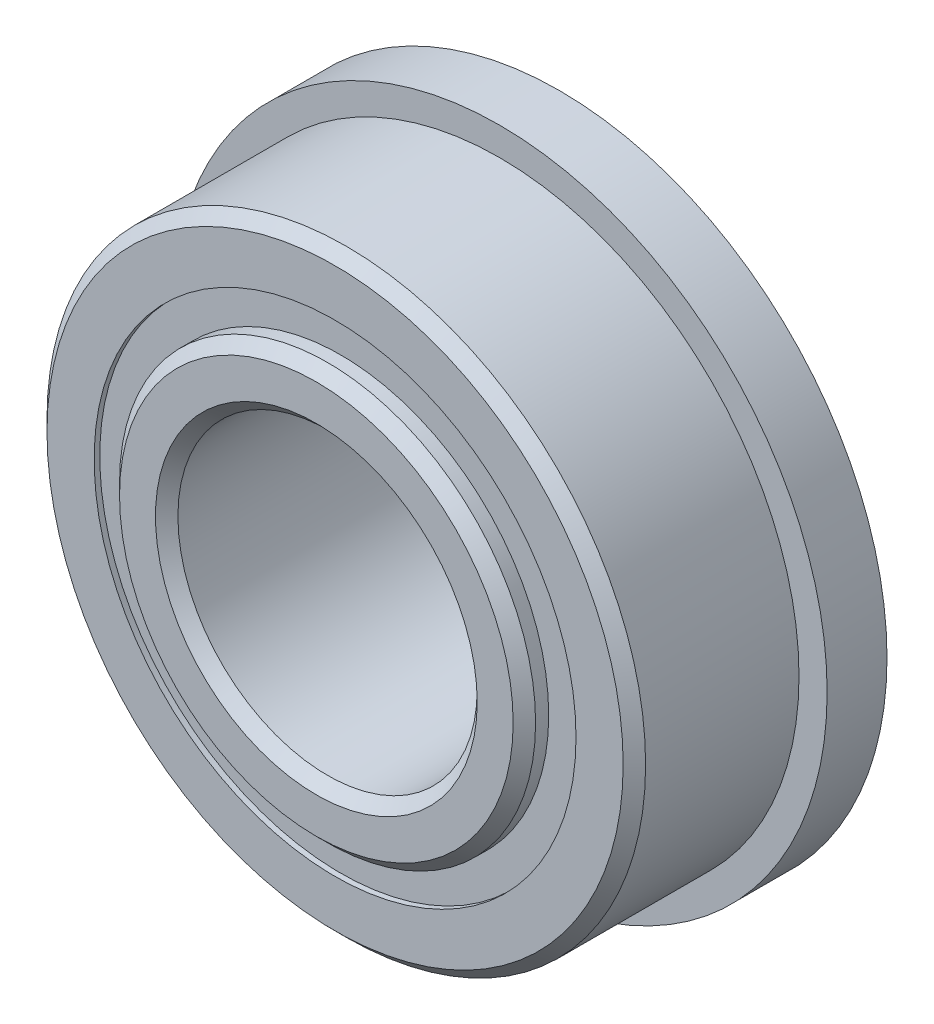
SolidWorks part; units mm, degrees
ref_plane "Front Plane" through (0, 0, 0) normal (0, 0, 1) x (1, 0, 0)
ref_plane "Top Plane" through (0, 0, 0) normal (0, 1, 0) x (1, 0, 0)
ref_plane "Right Plane" through (0, 0, 0) normal (1, 0, 0) x (0, 0, -1)
sketch "Sketch1" plane through (0, 0, 0) normal (1, 0, 0) x (0, 0, -1)
  line L0 (-2.3813, 0) -> (2.3813, 0) construction
  line L1 (0, 6.35) -> (0, -6.35) construction
  line L2 (2.1431, 6.35) -> (-2.1431, 6.35)
  line L3 (-2.1431, 6.35) -> (-2.3813, 6.1119)
  line L4 (-2.3813, 6.1119) -> (-2.3813, 5.1114)
  line L5 (-2.3813, 5.1114) -> (-1.0583, 5.1114)
  line L6 (2.3813, 5.1114) -> (1.0583, 5.1114)
  line L7 (2.3813, 6.1119) -> (2.3813, 5.1114)
  line L8 (2.1431, 6.35) -> (2.3813, 6.1119)
  line L9 (0, 6.35) -> (0, 4.7625) construction
  line L10 (0, 4.7625) -> (0, 3.175) construction
  arc A0 (-1.0583, 5.1114) -> (1.0583, 5.1114) centre (0, 4.7625) cw
  point P14 (0, 3.175)
  dimension "D3" = 2.1167
  dimension "D1" = 45
  dimension "Width" = 4.7625
  dimension "OD" = 12.7
  dimension "D2" = 0.2381
  dimension "Shaft Dia" = 6.35
  dimension "D4" = 0.3489
revolve "Revolve1" add sketch "Sketch1" angle 360 about L0
sketch "Sketch3" plane through (0, 0, 0) normal (1, 0, 0) x (0, 0, -1)
  line L0 (-1.0583, 4.4136) -> (-2.7788, 4.4136) construction
  line L1 (-2.3813, 6.1119) -> (-2.3813, 5.1114) construction
  line L2 (-2.1431, 6.35) -> (-2.3813, 6.1119) construction
  line L3 (-2.7788, 4.4136) -> (-2.7788, 3.4131) construction
  line L4 (-2.7788, 3.4131) -> (-2.7788, 4.1755)
  line L5 (-2.7788, 3.4131) -> (-2.5406, 3.175)
  line L6 (-2.5406, 3.175) -> (2.5406, 3.175)
  line L8 (2.5406, 3.175) -> (2.7788, 3.4131)
  line L10 (2.7788, 3.4131) -> (2.7788, 4.4136) construction
  line L11 (2.7788, 4.4136) -> (1.0583, 4.4136) construction
  line L12 (0, 6.35) -> (0, -6.35) construction
  line L13 (2.1431, 6.35) -> (2.3813, 6.1119) construction
  line L14 (-2.7788, 4.1755) -> (-2.5406, 4.4136)
  line L15 (-2.5406, 4.4136) -> (-1.0583, 4.4136)
  line L16 (1.0583, 4.4136) -> (2.5406, 4.4136)
  line L17 (2.5406, 4.4136) -> (2.7788, 4.1755)
  line L18 (2.7788, 4.1755) -> (2.7788, 3.4131)
  arc A1 (1.0583, 4.4136) -> (-1.0583, 4.4136) centre (0, 4.7625) cw
  arc A2 (1.0583, 5.1114) -> (-1.0583, 5.1114) centre (0, 4.7625) ccw construction
  dimension "D1" = 45
  dimension "Ring Wd" = 5.5575
revolve "Revolve3" add sketch "Sketch3" angle 360 about L0
sketch "Sketch4" plane through (0, 0, 0) normal (1, 0, 0) x (0, 0, -1)
  line L0 (-1.1144, 4.7625) -> (1.1144, 4.7625)
  arc A2 (-1.1144, 4.7625) -> (1.1144, 4.7625) centre (0, 4.7625) cw
  arc A3 (1.0583, 5.1114) -> (-1.0583, 5.1114) centre (0, 4.7625) ccw construction
revolve "Revolve4" add sketch "Sketch4" angle 360 about L0
ref_axis "Axis1" through (0, 0, -2.3813) along (0, 0, 1)
pattern_circular "CirPattern1" count 12 every 30 about axis through (0, 0, -2.3813) along (0, 0, 1) of bodies 104
sketch "Sketch5" plane through (0, 0, 0) normal (1, 0, 0) x (0, 0, -1)
  line L0 (-2.3813, 5.1114) -> (-1.0583, 5.1114) construction
  line L1 (-2.2622, 5.1114) -> (-1.1144, 5.1114)
  line L2 (-2.2622, 5.1114) -> (-2.2622, 4.4136)
  line L3 (-2.2622, 4.4136) -> (-1.1144, 4.4136)
  line L4 (-1.1144, 5.1114) -> (-1.1144, 4.4136)
  line L5 (-1.0583, 4.4136) -> (-2.7788, 4.4136) construction
  line L6 (2.3813, 5.1114) -> (1.0583, 5.1114) construction
  line L7 (2.2622, 5.1114) -> (1.1144, 5.1114)
  line L8 (2.2622, 5.1114) -> (2.2622, 4.4136)
  line L9 (2.2622, 4.4136) -> (1.1144, 4.4136)
  line L10 (1.1144, 5.1114) -> (1.1144, 4.4136)
  line L11 (2.7788, 4.4136) -> (1.0583, 4.4136) construction
  line L12 (-2.1431, 6.35) -> (-2.3813, 6.1119) construction
  point P18 (-2.2622, 6.2309)
revolve "Revolve5" add sketch "Sketch5" angle 360 about L0
sketch "Sketch6" plane through (0, 0, 0) normal (1, 0, 0) x (0, 0, -1)
  line L1 (2.3813, 5.1114) -> (1.1113, 5.1114)
  line L2 (2.3813, 5.1114) -> (2.3813, 6.9469)
  line L3 (2.3813, 6.9469) -> (1.1113, 6.9469)
  line L4 (1.1113, 5.1114) -> (1.1113, 6.9469)
  line L5 (2.3813, 0) -> (-2.3813, 0) construction
  dimension "Flange OD" = 13.8938
  dimension "Th" = 1.27
revolve "Revolve6" add sketch "Sketch6" angle 360 about L5
equation "\"D2@Sketch1\" = \"Width@Sketch1\"*.05"
equation "\"D3@Sketch1\" = \"Width@Sketch1\"/2.25"
equation "\"D4@Sketch1\" = (((\"OD@Sketch1\"-\"Width@Sketch1\")/2)/3.25)/3.5"
equation "\"D2@CirPattern1\" = 360/\"Balls@CirPattern1\""
